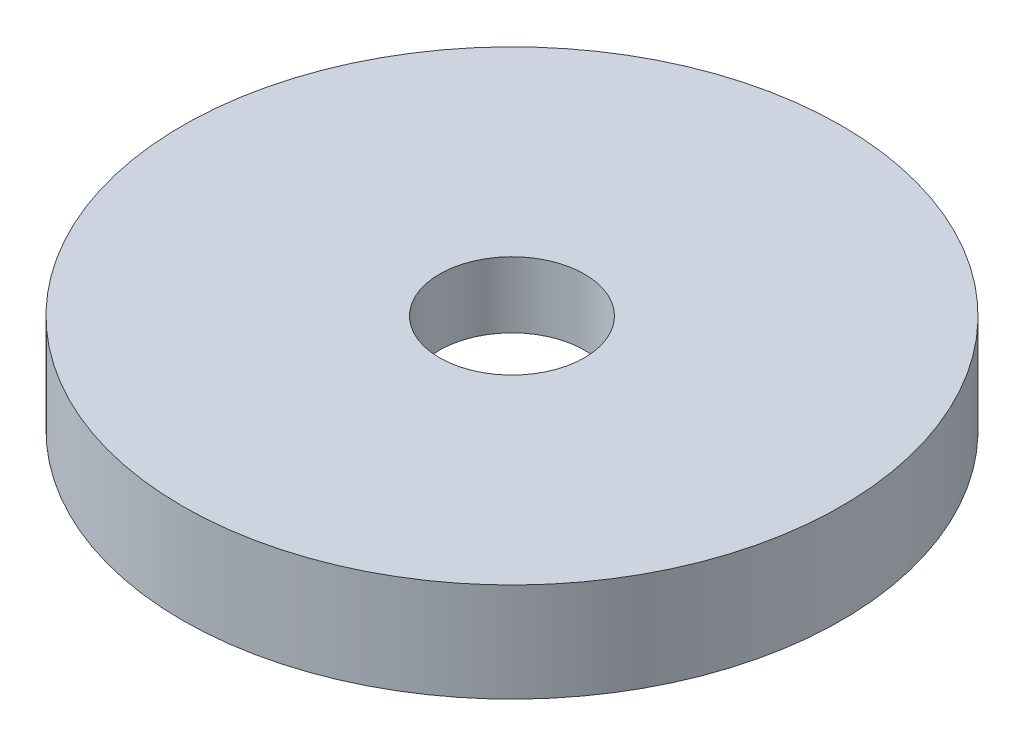
SolidWorks part; units mm, degrees
ref_plane "Front Plane" through (0, 0, 0) normal (0, 0, 1) x (1, 0, 0)
ref_plane "Top Plane" through (0, 0, 0) normal (0, 1, 0) x (1, 0, 0)
ref_plane "Right Plane" through (0, 0, 0) normal (1, 0, 0) x (0, 0, -1)
sketch "Sketch1" plane through (0, 0, 0) normal (0, 1, 0) x (1, 0, 0)
  circle A0 centre (0, 0) radius 5
  circle A1 centre (0, 0) radius 1.1
  circle A2 centre (0, 0) radius 2.5
  dimension "D1" = 10
  dimension "D2" = 2.2
  dimension "D3" = 5
extrude "Boss-Extrude1" add sketch "Sketch1" along normal blind 1.5 contours A0 A2 | A2 A1 region at (-4.8586, 0, 0) region at (-2.4293, 0, 0)
extrude "Cut-Extrude1" cut sketch "Sketch1<3>" along normal blind 0.5 contours A2 A1 region at (-2.4293, 0, 0)
sketch "Sketch1<3>" plane through (0, 0, 0) normal (0, 1, 0) x (1, 0, 0) same geometry as "Sketch1"
